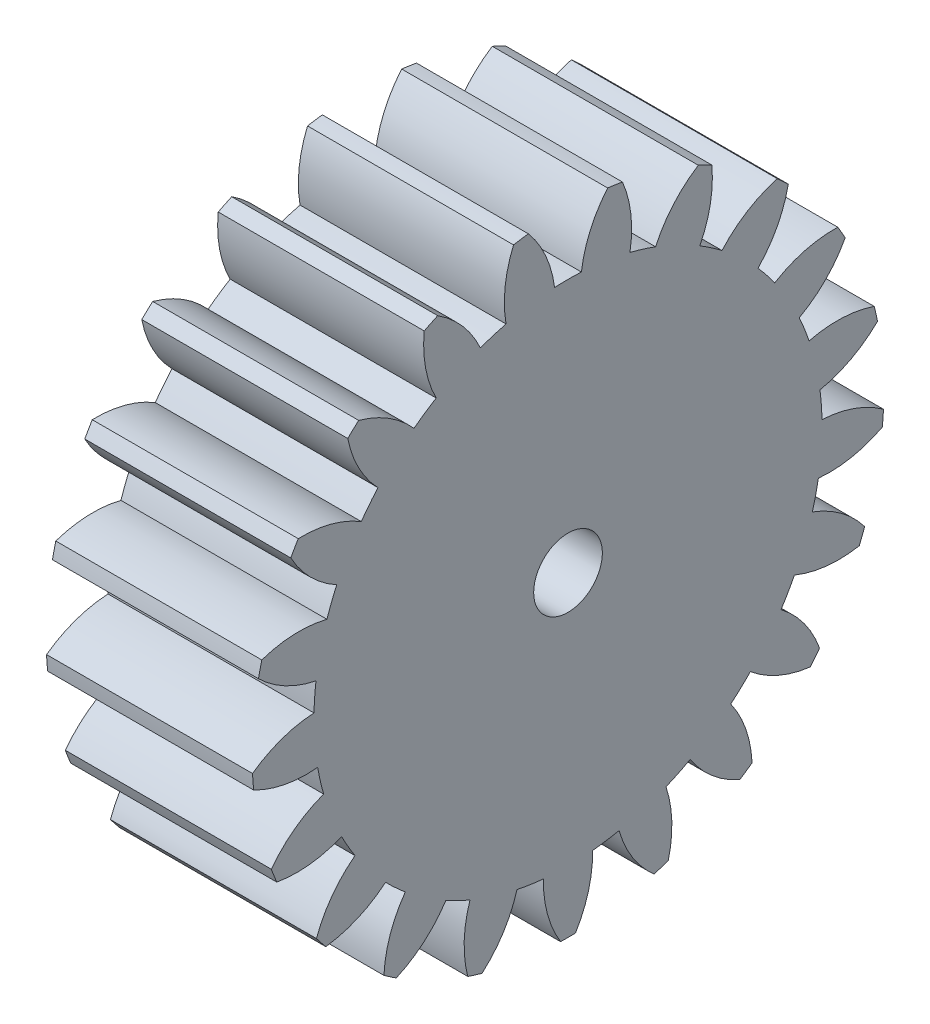
SolidWorks part; units mm, degrees
ref_plane "Plane1" through (0, 0, 0) normal (0, 0, 1) x (1, 0, 0)
ref_plane "Plane2" through (0, 0, 0) normal (0, 1, 0) x (1, 0, 0)
ref_plane "Plane3" through (0, 0, 0) normal (1, 0, 0) x (0, 0, -1)
other "Configuration Table"
sketch "HoldingSke" plane through (0, 0, 0) normal (0, 1, 0) x (1, 0, 0)
  line L0 (0, 0) -> (0.4668, -0.1792)
  line L1 (-15, 0) -> (100, 0) construction
  line L2 (0, 0) -> (-2.1039, 2.3779)
  line L3 (0, 0) -> (-11.863, 4.5341)
  line L4 (0, 0) -> (8.0624, 3.0949)
  line L5 (0, 0) -> (-46.8476, -17.4728)
  line L6 (0, 0) -> (-12.4344, -8.3896)
  line L7 (-2.1039, 2.3779) -> (8.6586, 51.2059)
  line L8 (-76.2, 54.61) -> (-75.3, 54.61)
  line L9 (-71.009, 38.7566) -> (-53.1078, 45.2721)
  line L10 (-76.2, 71.12) -> (104.1128, 71.12)
  line L11 (0, 0) -> (-15, 0)
  line L12 (-76.2, 101.6) -> (-76.133, 101.6)
  line L13 (24.9733, 27.94) -> (52.9518, 28.4284)
  line L14 (24.9733, 27.94) -> (24.9743, 27.94)
  line L15 (24.9733, 27.94) -> (100.4006, 29.5858)
  line L16 (-63.627, -2) -> (-12.827, -2)
  circle A0 centre (0, 0) radius 2.5
  circle A1 centre (0, 0) radius 18.499
  circle A2 centre (0, 0) radius 37.5
  circle A3 centre (0, 0) radius 2.5
  dimension "Num_teeth" = 21
  dimension "Pitch_radius" = 180.3128
  dimension "Width" = 15
  dimension "Thickness" = 15
sketch "BasProSke" plane through (0, 0, 0) normal (0, 1, 0) x (1, 0, 0)
  line L0 (-10, 0) -> (60, 0) construction
  line L1 (0, 0) -> (0, 23)
  line L2 (0, 0) -> (15, 0)
  line L3 (15, 0) -> (15, 23)
  line L4 (15, 23) -> (0, 23)
  dimension "Thickness" = 15
  dimension "Diameter" = 46
revolve "Base-Revolve" add sketch "BasProSke" angle 360 about L0
sketch "TooCutSke" plane through (0, 0, 0) normal (1, 0, 0) x (0, 0, -1)
  line L1 (0, 0) -> (0, 107) construction
  line L2 (0, 0) -> (-1.6865, 20.9322) construction
  line L3 (0, 0) -> (-6.2448, 41.4315) construction
  line L4 (-1.6865, 20.9322) -> (-3.1224, 20.7157) construction
  arc A0 (0.9768, 18.4732) -> (-0.9768, 18.4732) centre (0, 0) ccw
  arc A1 (2.908, 22.841) -> (-2.908, 22.841) centre (0, 0) ccw
  circle A2 centre (0, 0) radius 21 construction
  circle A3 centre (0, 0) radius 19.7335 construction
  arc A4 (-0.9768, 18.4732) -> (-2.908, 22.841) centre (-9.308, 17.4004) ccw
  arc A5 (2.908, 22.841) -> (0.9768, 18.4732) centre (9.308, 17.4004) ccw
extrude "ToothCut" cut sketch "TooCutSke" along normal through all
fillet "Breaks" [suppressed] radius 0.04 tangent propagation no
fillet "RootFillets" [suppressed] radius 0.501
pattern_circular "TeethCuts" count 21 every 17.143 about axis through (-10, 0, 0) along (1, 0, 0) of "ToothCut", "RootFillets", "Breaks"
sketch "HubNeaOneSke" plane through (0, 0, 0) normal (-1, 0, 0) x (0, 0, 1)
  circle A0 centre (0, 0) radius 18.499
  dimension "Diameter" = 36.998
extrude "HubNearOne" [suppressed] add sketch "HubNeaOneSke" along normal blind 35.0001
sketch "HubNeaBotSke" plane through (0, 0, 0) normal (-1, 0, 0) x (0, 0, 1)
  circle A0 centre (0, 0) radius 18.499
  dimension "Diameter" = 36.998
extrude "HubNearBoth" [suppressed] add sketch "HubNeaBotSke" along normal blind 17.5
ref_plane "FarPln" through (15, 0, 0) normal (1, 0, 0) x (0, 0, -1)
sketch "HubFarSke" plane through (15, 0, 0) normal (1, 0, 0) x (0, 0, -1)
  circle A0 centre (0, 0) radius 18.499
  dimension "Diameter" = 36.998
extrude "HubFar" [suppressed] add sketch "HubFarSke" along normal blind 17.5
sketch "BorSke" plane through (0, 0, 0) normal (1, 0, 0) x (0, 0, -1)
  circle A0 centre (0, 0) radius 2.5
extrude "Bore" cut sketch "BorSke" along normal mid plane 100.0001
sketch "KeySke" plane through (0, 0, 0) normal (1, 0, 0) x (0, 0, -1)
  line L0 (-1, 0) -> (-1, 3.4)
  line L1 (-1, 3.4) -> (1, 3.4)
  line L2 (1, 3.4) -> (1, 0)
  line L3 (0, 0) -> (0, 34) construction
  line L4 (-1, 0) -> (1, 0)
extrude "Keyway" [suppressed] cut sketch "KeySke" along normal mid plane 100.0001
pattern_circular "Keyway2" [suppressed] count 2 every 90 about axis through (-10, 0, 0) along (1, 0, 0)
equation "' \"Module@HoldingSke\" = 6.35"
equation "' \"Num_teeth@HoldingSke\" = 12"
equation "' \"Ap@HoldingSke\" =  20"
equation "' \"Ap@HoldingSke\" = 20"
equation "' \"Width@HoldingSke\" = 0.5 * 25.4"
equation "' \"Hub_dia@HoldingSke\"= 1 * 25.4"
equation "' \"Hub_dia@HoldingSke\" = 1 * 25.4"
equation "' \"Overall_len@HoldingSke\" = 1.0 * 25.4"
equation "' \"Bore@HoldingSke\" = 0.75 * 25.4"
equation "' \"T_dim@HoldingSke\" = 0.1 * 25.4"
equation "' \"Width@KeySke\" = 0.25 * 25.4"
equation "' \"Show_teeth@HoldingSke\" = 13"
equation "' \"Backlash@HoldingSke\" = 0.009 * 25.4"
equation "' \"Addendum_fac@HoldingSke\" = 1.0"
equation "' \"Dedendum_fac@HoldingSke\" = 1.25"
equation "' \"Dedendum_add@HoldingSke\" = 0.00005 * 25.4"
equation "' \"Clearance_fac@HoldingSke\" = 0.25"
equation "\"Pitch@HoldingSke\" = 1 / \"Module@HoldingSke\""
equation "\"Overcut_dia@TooCutSke\" = (\"Num_teeth@HoldingSke\" + 2 * \"Addendum_fac@HoldingSke\") / \"Pitch@HoldingSke\" + 0.002 * 25.4"
equation "\"Pitch_dia@TooCutSke\" = \"Num_teeth@HoldingSke\" / \"Pitch@HoldingSke\""
equation "\"Base_dia@TooCutSke\" = \"Num_teeth@HoldingSke\" / \"Pitch@HoldingSke\" * cos((\"Ap@HoldingSke\"  * 3.14159265 / 180))"
equation "\"Root_dia@TooCutSke\" = (\"Num_teeth@HoldingSke\" + 2) / \"Pitch@HoldingSke\" - 2 * (\"Addendum_fac@HoldingSke\" + \"Dedendum_fac@HoldingSke\") / \"Pitch@HoldingSke\" - \"Dedendum_add@HoldingSke\" * 2"
equation "\"Half_ang@TooCutSke\" = 180 / \"Num_teeth@HoldingSke\""
equation "\"Half_CT@TooCutSke\" = \"Num_teeth@HoldingSke\" / \"Pitch@HoldingSke\" * sin((3.14159265 / 2 / \"Num_teeth@HoldingSke\")) / 2 - 7 * \"Backlash@HoldingSke\" / 4"
equation "\"Flank_rad@TooCutSke\" = \"Num_teeth@HoldingSke\" / \"Pitch@HoldingSke\" / 5"
equation "\"Radius@RootFillets\" = \"Clearance_fac@HoldingSke\" / \"Pitch@HoldingSke\" + \"Dedendum_add@HoldingSke\""
equation "\"Break_rad@Breaks\" = 0.02 / \"Pitch@HoldingSke\""
equation "\"Thickness@HoldingSke\" = \"Width@HoldingSke\""
equation "\"OAL@HoldingSke\" = \"Thickness@HoldingSke\""
equation "\"MHD@HoldingSke\" = (\"Num_teeth@HoldingSke\" + 2) / \"Pitch@HoldingSke\" - 2 * (\"Addendum_fac@HoldingSke\" + \"Dedendum_fac@HoldingSke\")  / \"Pitch@HoldingSke\" - \"Dedendum_add@HoldingSke\" * 2"
equation "\"MBD@HoldingSke\" = (\"Num_teeth@HoldingSke\" + 2) / \"Pitch@HoldingSke\" - 2 * (\"Addendum_fac@HoldingSke\" + \"Dedendum_fac@HoldingSke\")  / \"Pitch@HoldingSke\" - \"Dedendum_add@HoldingSke\" * 2 - 0.002 * 25.4"
equation "\"MHD@HoldingSke\" = ((sgn( \"MHD@HoldingSke\" - \"Hub_dia@HoldingSke\" )-1)*( \"MHD@HoldingSke\" - \"Hub_dia@HoldingSke\" ))/-2+ \"Hub_dia@HoldingSke\""
equation "\"MBD@HoldingSke\" = ((sgn( \"MBD@HoldingSke\" - \"Bore@HoldingSke\" )-1)*( \"MBD@HoldingSke\" - \"Bore@HoldingSke\" ))/-2+ \"Bore@HoldingSke\""
equation "\"OAL@HoldingSke\" = ((sgn( \"OAL@HoldingSke\" - \"Overall_len@HoldingSke\" )+1)*( \"OAL@HoldingSke\" - \"Overall_len@HoldingSke\" ))/2 + \"Overall_len@HoldingSke\" + 0.000002 * 25.4"
equation "\"Num_teeth@TeethCuts\" = int( \"Show_teeth@HoldingSke\" ) + 1"
equation "\"Num_teeth@TeethCuts\" = ((sgn( \"Num_teeth@TeethCuts\" - \"Num_teeth@HoldingSke\" )-1)*( \"Num_teeth@TeethCuts\" - \"Num_teeth@HoldingSke\" ))/-2+ \"Num_teeth@HoldingSke\""
equation "\"Num_teeth@TeethCuts\" = ((sgn( \"Num_teeth@TeethCuts\" - 2.0)+1)*( \"Num_teeth@TeethCuts\" - 2.0))/2 +2.0"
equation "\"Angle@TeethCuts\" = 360.0 / \"Num_teeth@HoldingSke\""
equation "\"Diameter@BasProSke\" = (\"Num_teeth@HoldingSke\" + 2 * \"Addendum_fac@HoldingSke\") / \"Pitch@HoldingSke\""
equation "\"Thickness@BasProSke\"  = \"Thickness@HoldingSke\""
equation "' \"Fillet_rad@BasProSke\" =  \"Thickness@HoldingSke\" * 0.05"
equation "' \"Fillet_rad@BasProSke\" = \"Thickness@HoldingSke\" * 0.05"
equation "\"MHD@HoldingSke\" = ((sgn( \"MHD@HoldingSke\" - \"Root_dia@TooCutSke\" )-1)*( \"MHD@HoldingSke\" - \"Root_dia@TooCutSke\" ))/-2+ \"Root_dia@TooCutSke\""
equation "\"Diameter@HubNeaOneSke\" = \"MHD@HoldingSke\""
equation "\"Length@HubNearOne\" = \"OAL@HoldingSke\" - \"Thickness@BasProSke\""
equation "\"Diameter@HubNeaBotSke\" = \"MHD@HoldingSke\""
equation "\"Length@HubNearBoth\" = ( \"OAL@HoldingSke\" - \"Thickness@BasProSke\" ) / 2.0"
equation "\"Thickness@FarPln\" = \"Thickness@BasProSke\""
equation "\"Diameter@HubFarSke\" = \"MHD@HoldingSke\""
equation "\"Length@HubFar\" = ( \"OAL@HoldingSke\" - \"Thickness@BasProSke\" ) / 2.0"
equation "\"Diameter@BorSke\" = \"MBD@HoldingSke\""
equation "\"D1@Bore\" = \"OAL@HoldingSke\" * 2.0"
equation "\"D1@Keyway\" = \"OAL@HoldingSke\" * 2.0"
equation "\"Offset@KeySke\" = \"T_dim@HoldingSke\" + \"MBD@HoldingSke\" / 2.0"
